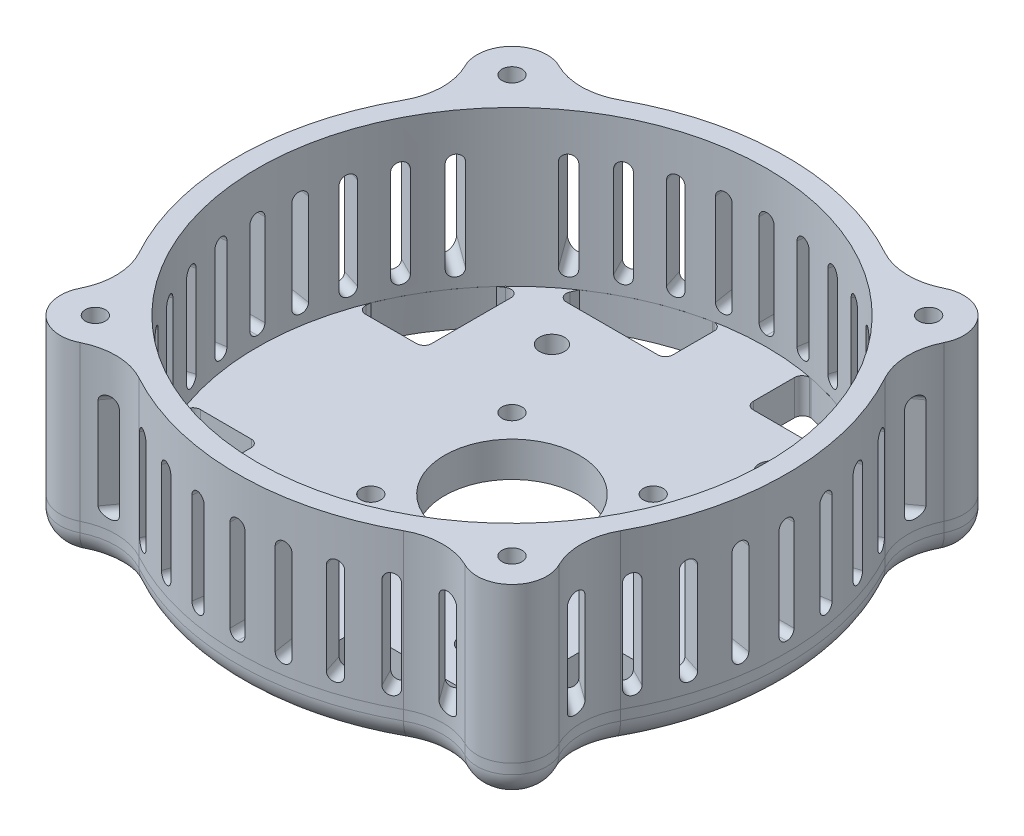
SolidWorks part; units mm, degrees
ref_plane "Front Plane" through (0, 0, 0) normal (0, 0, 1) x (1, 0, 0)
ref_plane "Top Plane" through (0, 0, 0) normal (0, 1, 0) x (1, 0, 0)
ref_plane "Right Plane" through (0, 0, 0) normal (1, 0, 0) x (0, 0, -1)
sketch "Sketch1" plane through (0, 0, 0) normal (0, 1, 0) x (1, 0, 0)
  circle A0 centre (0, 0) radius 51
  arc A1 (48.2016, -26.4879) -> (48.2016, 26.4879) centre (0, 0) ccw
  circle A2 centre (41.7193, -41.7193) radius 2
  arc A3 (38.5796, -47.9757) -> (47.9757, -38.5796) centre (41.7193, -41.7193) ccw
  arc A4 (47.9757, -38.5796) -> (48.2016, -26.4879) centre (59.5947, -32.7487) cw
  arc A5 (38.5796, -47.9757) -> (26.4879, -48.2016) centre (32.7487, -59.5947) ccw
  arc A6 (-47.9757, -38.5796) -> (-48.2016, -26.4879) centre (-59.5947, -32.7487) ccw
  arc A7 (-47.9757, -38.5796) -> (-38.5796, -47.9757) centre (-41.7193, -41.7193) ccw
  arc A8 (-38.5796, -47.9757) -> (-26.4879, -48.2016) centre (-32.7487, -59.5947) cw
  arc A9 (-38.5796, 47.9757) -> (-26.4879, 48.2016) centre (-32.7487, 59.5947) ccw
  arc A10 (-38.5796, 47.9757) -> (-47.9757, 38.5796) centre (-41.7193, 41.7193) ccw
  arc A11 (-47.9757, 38.5796) -> (-48.2016, 26.4879) centre (-59.5947, 32.7487) cw
  arc A12 (47.9757, 38.5796) -> (48.2016, 26.4879) centre (59.5947, 32.7487) ccw
  arc A13 (47.9757, 38.5796) -> (38.5796, 47.9757) centre (41.7193, 41.7193) ccw
  arc A14 (38.5796, 47.9757) -> (26.4879, 48.2016) centre (32.7487, 59.5947) cw
  arc A15 (-26.4879, -48.2016) -> (26.4879, -48.2016) centre (0, 0) ccw
  arc A16 (-48.2016, 26.4879) -> (-48.2016, -26.4879) centre (0, 0) ccw
  arc A17 (26.4879, 48.2016) -> (-26.4879, 48.2016) centre (0, 0) ccw
  circle A18 centre (-41.7193, -41.7193) radius 2
  circle A19 centre (-41.7193, 41.7193) radius 2
  circle A20 centre (41.7193, 41.7193) radius 2
  point P43 (0, 0)
  point P46 (0, 0)
  dimension "D1" = 13
  dimension "D2" = 4
  dimension "D3" = 4
extrude "Boss-Extrude1" add sketch "Sketch1" along normal blind 31
sketch "Sketch2" plane through (0, 0, 0) normal (0, -1, 0) x (1, 0, 0)
  line L0 (-27.1923, -38.7625) -> (-9.5503, -38.7625)
  line L1 (-8.0503, -40.2625) -> (-8.0503, -48.5407)
  line L2 (-9.5503, -50.0407) -> (-9.8455, -50.0407)
  line L3 (-27.1923, -38.7625) -> (-27.8921, -38.7625)
  line L4 (-29.2644, -40.8681) -> (-28.6929, -42.163)
  line L5 (-13.5, 0) -> (13.5, 0) construction
  line L6 (0, 13.5) -> (0, -13.5) construction
  line L7 (9.5503, -50.0407) -> (9.8455, -50.0407)
  line L8 (8.0503, -40.2625) -> (8.0503, -48.5407)
  line L9 (27.1923, -38.7625) -> (27.8921, -38.7625)
  line L10 (27.1923, -38.7625) -> (9.5503, -38.7625)
  line L11 (29.2644, -40.8681) -> (28.6929, -42.163)
  line L12 (29.2644, 40.8681) -> (28.6929, 42.163)
  line L13 (27.1923, 38.7625) -> (27.8921, 38.7625)
  line L14 (27.1923, 38.7625) -> (9.5503, 38.7625)
  line L15 (8.0503, 40.2625) -> (8.0503, 48.5407)
  line L16 (9.5503, 50.0407) -> (9.8455, 50.0407)
  line L17 (-9.5503, 50.0407) -> (-9.8455, 50.0407)
  line L18 (-8.0503, 40.2625) -> (-8.0503, 48.5407)
  line L19 (-29.2644, 40.8681) -> (-28.6929, 42.163)
  line L20 (-27.1923, 38.7625) -> (-27.8921, 38.7625)
  line L21 (-27.1923, 38.7625) -> (-9.5503, 38.7625)
  line L22 (34.162, -33.9483) -> (34.162, -18.0531)
  line L23 (35.6576, -16.5532) -> (45.8759, -16.5235)
  line L24 (36.4859, -35.2018) -> (37.5697, -34.4894)
  line L25 (47.3753, -18.1451) -> (47.2999, -19.0714)
  line L26 (47.3753, 18.1451) -> (47.2999, 19.0714)
  line L27 (35.6576, 16.5532) -> (45.8759, 16.5235)
  line L28 (34.162, 33.9483) -> (34.162, 18.0531)
  line L29 (36.4859, 35.2018) -> (37.5697, 34.4894)
  line L30 (-36.4859, 35.2018) -> (-37.5697, 34.4894)
  line L31 (-34.162, 33.9483) -> (-34.162, 18.0531)
  line L32 (-35.6576, 16.5532) -> (-45.8759, 16.5235)
  line L33 (-47.3753, 18.1451) -> (-47.2999, 19.0714)
  line L34 (-47.3753, -18.1451) -> (-47.2999, -19.0714)
  line L35 (-35.6576, -16.5532) -> (-45.8759, -16.5235)
  line L36 (-34.162, -33.9483) -> (-34.162, -18.0531)
  line L37 (-36.4859, -35.2018) -> (-37.5697, -34.4894)
  circle A0 centre (0, 0) radius 51 construction
  circle A1 centre (-41.7193, 41.7193) radius 2
  circle A2 centre (-41.7193, 41.7193) radius 2
  circle A3 centre (0, 0) radius 51
  circle A4 centre (-41.7193, -41.7193) radius 2 construction
  circle A5 centre (-41.7193, -41.7193) radius 2
  circle A6 centre (41.7193, 41.7193) radius 2 construction
  circle A7 centre (41.7193, 41.7193) radius 2
  circle A8 centre (41.7193, -41.7193) radius 2 construction
  circle A9 centre (41.7193, -41.7193) radius 2
  circle A10 centre (0, 0) radius 13.5
  arc A11 (-8.0503, -48.5407) -> (-9.5503, -50.0407) centre (-9.5503, -48.5407) cw
  arc A12 (-9.5503, -38.7625) -> (-8.0503, -40.2625) centre (-9.5503, -40.2625) cw
  arc A13 (-27.8921, -38.7625) -> (-29.2644, -40.8681) centre (-27.8921, -40.2625) ccw
  arc A14 (8.0503, -48.5407) -> (9.5503, -50.0407) centre (9.5503, -48.5407) ccw
  arc A15 (9.5503, -38.7625) -> (8.0503, -40.2625) centre (9.5503, -40.2625) ccw
  arc A16 (27.8921, -38.7625) -> (29.2644, -40.8681) centre (27.8921, -40.2625) cw
  arc A17 (27.8921, 38.7625) -> (29.2644, 40.8681) centre (27.8921, 40.2625) ccw
  arc A18 (47.9757, 38.5796) -> (48.2016, 26.4879) centre (59.5947, 32.7487) ccw
  arc A19 (47.9757, 38.5796) -> (38.5796, 47.9757) centre (41.7193, 41.7193) ccw
  arc A20 (26.4879, 48.2016) -> (38.5796, 47.9757) centre (32.7487, 59.5947) ccw
  arc A21 (26.4879, 48.2016) -> (-26.4879, 48.2016) centre (0, 0) ccw
  arc A22 (-38.5796, 47.9757) -> (-26.4879, 48.2016) centre (-32.7487, 59.5947) ccw
  arc A23 (-38.5796, 47.9757) -> (-47.9757, 38.5796) centre (-41.7193, 41.7193) ccw
  arc A24 (-48.2016, 26.4879) -> (-47.9757, 38.5796) centre (-59.5947, 32.7487) ccw
  arc A25 (-48.2016, 26.4879) -> (-48.2016, -26.4879) centre (0, 0) ccw
  arc A26 (-47.9757, -38.5796) -> (-48.2016, -26.4879) centre (-59.5947, -32.7487) ccw
  arc A27 (-47.9757, -38.5796) -> (-38.5796, -47.9757) centre (-41.7193, -41.7193) ccw
  arc A28 (-26.4879, -48.2016) -> (-38.5796, -47.9757) centre (-32.7487, -59.5947) ccw
  arc A29 (-26.4879, -48.2016) -> (26.4879, -48.2016) centre (0, 0) ccw
  arc A30 (38.5796, -47.9757) -> (26.4879, -48.2016) centre (32.7487, -59.5947) ccw
  arc A31 (38.5796, -47.9757) -> (47.9757, -38.5796) centre (41.7193, -41.7193) ccw
  arc A32 (48.2016, -26.4879) -> (47.9757, -38.5796) centre (59.5947, -32.7487) ccw
  arc A33 (48.2016, -26.4879) -> (48.2016, 26.4879) centre (0, 0) ccw
  arc A34 (47.9757, 38.5796) -> (48.2016, 26.4879) centre (59.5947, 32.7487) ccw
  arc A35 (47.9757, 38.5796) -> (38.5796, 47.9757) centre (41.7193, 41.7193) ccw
  arc A36 (26.4879, 48.2016) -> (38.5796, 47.9757) centre (32.7487, 59.5947) ccw
  arc A37 (26.4879, 48.2016) -> (-26.4879, 48.2016) centre (0, 0) ccw
  arc A38 (-38.5796, 47.9757) -> (-26.4879, 48.2016) centre (-32.7487, 59.5947) ccw
  arc A39 (-38.5796, 47.9757) -> (-47.9757, 38.5796) centre (-41.7193, 41.7193) ccw
  arc A40 (-48.2016, 26.4879) -> (-47.9757, 38.5796) centre (-59.5947, 32.7487) ccw
  arc A41 (-48.2016, 26.4879) -> (-48.2016, -26.4879) centre (0, 0) ccw
  arc A42 (-47.9757, -38.5796) -> (-48.2016, -26.4879) centre (-59.5947, -32.7487) ccw
  arc A43 (-47.9757, -38.5796) -> (-38.5796, -47.9757) centre (-41.7193, -41.7193) ccw
  arc A44 (-26.4879, -48.2016) -> (-38.5796, -47.9757) centre (-32.7487, -59.5947) ccw
  arc A45 (-26.4879, -48.2016) -> (26.4879, -48.2016) centre (0, 0) ccw
  arc A46 (38.5796, -47.9757) -> (26.4879, -48.2016) centre (32.7487, -59.5947) ccw
  arc A47 (38.5796, -47.9757) -> (47.9757, -38.5796) centre (41.7193, -41.7193) ccw
  arc A48 (48.2016, -26.4879) -> (47.9757, -38.5796) centre (59.5947, -32.7487) ccw
  arc A49 (48.2016, -26.4879) -> (48.2016, 26.4879) centre (0, 0) ccw
  arc A50 (9.5503, 38.7625) -> (8.0503, 40.2625) centre (9.5503, 40.2625) cw
  arc A51 (8.0503, 48.5407) -> (9.5503, 50.0407) centre (9.5503, 48.5407) cw
  arc A52 (-8.0503, 48.5407) -> (-9.5503, 50.0407) centre (-9.5503, 48.5407) ccw
  arc A53 (-27.8921, 38.7625) -> (-29.2644, 40.8681) centre (-27.8921, 40.2625) cw
  arc A54 (-9.5503, 38.7625) -> (-8.0503, 40.2625) centre (-9.5503, 40.2625) ccw
  arc A55 (34.162, -33.9483) -> (36.4859, -35.2018) centre (35.662, -33.9483) ccw
  arc A56 (45.8759, -16.5235) -> (47.3753, -18.1451) centre (45.8802, -18.0235) cw
  arc A57 (34.162, -18.0531) -> (35.6576, -16.5532) centre (35.662, -18.0531) cw
  arc A58 (45.8759, 16.5235) -> (47.3753, 18.1451) centre (45.8802, 18.0235) ccw
  arc A59 (34.162, 18.0531) -> (35.6576, 16.5532) centre (35.662, 18.0531) ccw
  arc A60 (34.162, 33.9483) -> (36.4859, 35.2018) centre (35.662, 33.9483) cw
  arc A61 (-34.162, 33.9483) -> (-36.4859, 35.2018) centre (-35.662, 33.9483) ccw
  arc A62 (-34.162, 18.0531) -> (-35.6576, 16.5532) centre (-35.662, 18.0531) cw
  arc A63 (-45.8759, 16.5235) -> (-47.3753, 18.1451) centre (-45.8802, 18.0235) cw
  arc A64 (-45.8759, -16.5235) -> (-47.3753, -18.1451) centre (-45.8802, -18.0235) ccw
  arc A65 (-34.162, -18.0531) -> (-35.6576, -16.5532) centre (-35.662, -18.0531) ccw
  arc A66 (-34.162, -33.9483) -> (-36.4859, -35.2018) centre (-35.662, -33.9483) cw
  circle A67 centre (-14.1326, 14.1421) radius 2
  circle A68 centre (14.1421, 14.1326) radius 2
  circle A69 centre (14.1326, -14.1421) radius 2
  circle A70 centre (-14.1421, -14.1326) radius 2
  circle A71 centre (21.9771, 29.9721) radius 2.5
  circle A72 centre (-21.9771, 29.9721) radius 2.5
  circle A73 centre (21.9771, -29.9721) radius 2.5
  circle A74 centre (-21.9771, -29.9721) radius 2.5
  point P72 (-28.9786, -41.5155)
  point P90 (-28.9786, 41.5155)
  point P154 (0, 0)
  circle M19 centre (-41.7193, -41.7193) radius 2
  circle M20 centre (41.7193, 41.7193) radius 2
  arc M21 (48.2016, 26.4879) -> (47.9757, 38.5796) centre (59.5947, 32.7487) cw
  arc M22 (47.9757, 38.5796) -> (38.5796, 47.9757) centre (41.7193, 41.7193) ccw
  arc M23 (38.5796, 47.9757) -> (26.4879, 48.2016) centre (32.7487, 59.5947) cw
  arc M24 (26.4879, 48.2016) -> (-26.4879, 48.2016) centre (0, 0) ccw
  arc M25 (-26.4879, 48.2016) -> (-38.5796, 47.9757) centre (-32.7487, 59.5947) cw
  arc M26 (-38.5796, 47.9757) -> (-47.9757, 38.5796) centre (-41.7193, 41.7193) ccw
  arc M27 (-47.9757, 38.5796) -> (-48.2016, 26.4879) centre (-59.5947, 32.7487) cw
  arc M28 (-48.2016, 26.4879) -> (-48.2016, -26.4879) centre (0, 0) ccw
  arc M29 (-48.2016, -26.4879) -> (-47.9757, -38.5796) centre (-59.5947, -32.7487) cw
  arc M30 (-47.9757, -38.5796) -> (-38.5796, -47.9757) centre (-41.7193, -41.7193) ccw
  arc M31 (-38.5796, -47.9757) -> (-26.4879, -48.2016) centre (-32.7487, -59.5947) cw
  arc M32 (-26.4879, -48.2016) -> (26.4879, -48.2016) centre (0, 0) ccw
  arc M33 (26.4879, -48.2016) -> (38.5796, -47.9757) centre (32.7487, -59.5947) cw
  arc M34 (38.5796, -47.9757) -> (47.9757, -38.5796) centre (41.7193, -41.7193) ccw
  arc M35 (47.9757, -38.5796) -> (48.2016, -26.4879) centre (59.5947, -32.7487) cw
  arc M36 (48.2016, -26.4879) -> (48.2016, 26.4879) centre (0, 0) ccw
  circle M37 centre (0, 0) radius 51
  circle M38 centre (-41.7193, 41.7193) radius 2
  circle M39 centre (41.7193, -41.7193) radius 2
  dimension "D3" = 1.5
  dimension "D4" = 1.5
  dimension "D5" = 4
  dimension "D6" = 5
  dimension "D7" = 4
  dimension "D1" = 0
  dimension "D2" = 0
extrude "Boss-Extrude2" add sketch "Sketch2" along normal blind 7 separate body contours L36 A66 L37 L4 A13 L3 L0 A12 L1 A11 L2 L7 A14 L8 A15 L10 L9 A16 L11 L24 A55 L22 A57 L23 A56 L25 L26 A58 L27 A59 L28 A60 L29 L12 A17 L13 L14 A50 L15 A51 L16 L17 A52 L18 A54 M37 | M36 M21 M22 M23 M24 M25 M26 M27 M28 M29 M30 M31 M32 M33 M34 M35 M20 M37 M39 M38 M19
fillet "Fillet1" radius 5 24 edges at (9.6979, -7, -50.0407) (47.3376, -7, -18.6083) (47.3376, -7, 18.6083) (9.6979, -7, 50.0407) (-9.6979, -7, 50.0407) (-47.3376, -7, -18.6083) (-47.3376, -7, 18.6083) (55, -7, 0) (46.5969, -7, 32.5059) (46.669, -7, 46.669) (32.5059, -7, 46.5969) (0, -7, 55) (-32.5059, -7, 46.5969) (-46.669, -7, 46.669) (-46.5969, -7, 32.5059) (-55, -7, 0) (-46.5969, -7, -32.5059) (-46.669, -7, -46.669) (-32.5059, -7, -46.5969) (0, -7, -55) (32.5059, -7, -46.5969) (46.669, -7, -46.669) (46.5969, -7, -32.5059) (-9.6979, -7, -50.0407)
sketch "Sketch3" plane through (0, 0, 0) normal (1, 0, 0) x (0, 0, -1)
  line L2 (-1.4239, 21.8827) -> (-1.4239, 3.5)
  line L4 (1.5, 21.8827) -> (1.5, 3.5)
  arc A0 (1.5, 21.8827) -> (-1.4239, 21.8827) centre (0.0381, 21.8827) ccw
  arc A1 (-1.4239, 3.5) -> (1.5, 3.5) centre (0.0381, 3.5) ccw
  dimension "D1" = 18.3827
  dimension "D2" = 1.4619
extrude "Cut-Extrude1" cut sketch "Sketch3" along normal blind 61
pattern_circular "CirPattern1" count 5 every 9 about axis through (0, 0, 0) along (0, 1, 0) of "Cut-Extrude1"
mirror "Mirror1" about plane through (0, 0, 0) normal (0, 0, 1) of "CirPattern1", "Cut-Extrude1"
mirror "Mirror2" about plane through (0, 0, 0) normal (1, 0, 0) of "Mirror1", "CirPattern1", "Cut-Extrude1"
pattern_circular "CirPattern2" count 2 every 90 about axis through (0, 31, 0) along (0, -1, 0) of "Mirror2", "Cut-Extrude1", "CirPattern1", "Mirror1"
sketch "Sketch4" plane through (0, -7, 0) normal (0, -1, 0) x (1, 0, 0)
  circle A0 centre (41.7193, 41.7193) radius 5
  circle A1 centre (41.7193, -41.7193) radius 5
  circle A2 centre (-41.7193, -41.7193) radius 5
  circle A3 centre (-41.7193, 41.7193) radius 5
  point P12 (0, 0)
  dimension "D1" = 10
  dimension "D2" = 4
extrude "Cut-Extrude2" cut sketch "Sketch4" against normal blind 15
